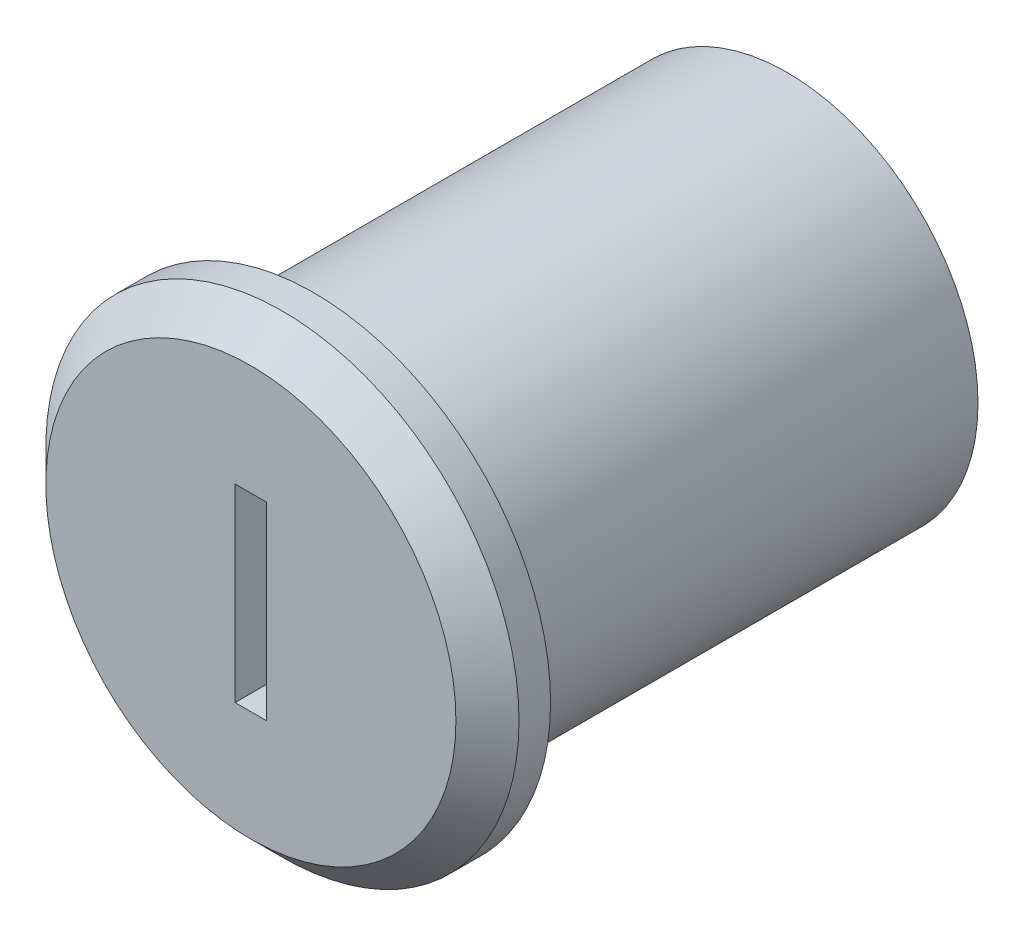
SolidWorks part; units mm, degrees
ref_plane "Front" through (0, 0, 0) normal (0, 0, 1) x (1, 0, 0)
ref_plane "Top" through (0, 0, 0) normal (0, 1, 0) x (1, 0, 0)
ref_plane "Right" through (0, 0, 0) normal (1, 0, 0) x (0, 0, -1)
sketch "Sketch1" plane through (0, 0, 0) normal (0, 0, 1) x (1, 0, 0)
  circle A0 centre (0, 0) radius 6.05
  dimension "D1" = 12.1
extrude "Boss-Extrude1" add sketch "Sketch1" against normal blind 15
sketch "Sketch2" plane through (0, 0, 0) normal (0, 0, 1) x (1, 0, 0)
  circle A0 centre (0, 0) radius 7.5
  dimension "D1" = 15
extrude "Boss-Extrude2" add sketch "Sketch2" along normal blind 1
sketch "Sketch3" plane through (0, 0, 1) normal (0, 0, 1) x (1, 0, 0)
  circle A1 centre (0, 0) radius 7.5
  circle A2 centre (0, 0) radius 7.5
  dimension "D1" = 0
extrude "Boss-Extrude3" add sketch "Sketch3" along normal blind 1 draft 45
sketch "Sketch4" plane through (0, 0, 2) normal (0, 0, 1) x (1, 0, 0)
  line L1 (-0.5, -3) -> (0.5, -3)
  line L2 (-0.5, -3) -> (-0.5, 3)
  line L3 (-0.5, 3) -> (0.5, 3)
  line L4 (0.5, -3) -> (0.5, 3)
  line L5 (-0.5, -3) -> (0.5, 3) construction
  line L6 (-0.5, 3) -> (0.5, -3) construction
  point P0 (0, 0)
  dimension "D1" = 1
  dimension "D2" = 6
extrude "Cut-Extrude1" cut sketch "Sketch4" against normal blind 1
